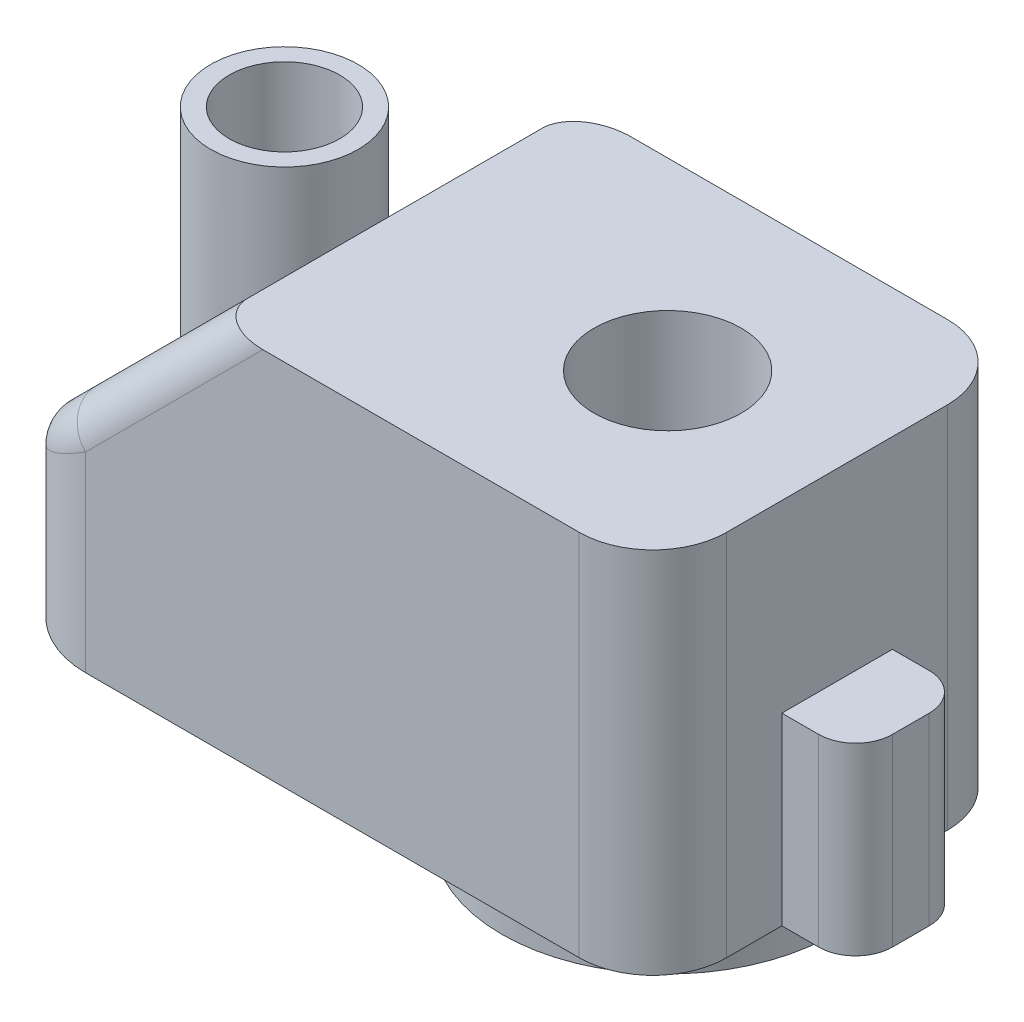
SolidWorks part; units mm, degrees
ref_plane "Alzado" through (0, 0, 0) normal (0, 0, 1) x (1, 0, 0)
ref_plane "Planta" through (0, 0, 0) normal (0, 1, 0) x (1, 0, 0)
ref_plane "Vista lateral" through (0, 0, 0) normal (1, 0, 0) x (0, 0, -1)
sketch "Croquis1" plane through (0, 0, 0) normal (0, 1, 0) x (1, 0, 0)
  line L1 (0, 0) -> (900, 0)
  line L2 (0, 0) -> (0, 500)
  line L3 (0, 500) -> (900, 500)
  line L4 (900, 0) -> (900, 500)
  dimension "D1" = 900
  dimension "D2" = 500
extrude "Saliente-Extruir1" add sketch "Croquis1" along normal blind 500
sketch "Croquis2" plane through (900, 0, 0) normal (1, 0, 0) x (0, 0, -1)
  line L0 (0, 0) -> (500, 0) construction
  line L1 (175, 250) -> (325, 250)
  line L2 (175, 250) -> (175, 0)
  line L3 (175, 0) -> (325, 0)
  line L4 (325, 250) -> (325, 0)
  line L5 (0, 500) -> (0, 0) construction
  point P6 (250, 250)
  dimension "D1" = 150
  dimension "D2" = 250
  dimension "D3" = 250
extrude "Saliente-Extruir2" add sketch "Croquis2" along normal blind 100 separate body
fillet "Redondeo1" radius 50 2 edges at (1000, 125, -325) (1000, 125, -175)
fillet "Redondeo2" radius 100 2 edges at (900, 250, -500) (900, 250, 0)
chamfer "Chaflán1" distance 300 angle 45 1 edges at (0, 500, -250)
fillet "Redondeo5" radius 130 2 edges at (0, 100, -500) (0, 100, 0)
sketch "Croquis3" plane through (0, 500, 0) normal (0, 1, 0) x (1, 0, 0)
  line L2 (130, 500) -> (300, 500) construction
  circle A0 centre (150, 250) radius 100
  dimension "D1" = 150
  dimension "D2" = 250
  dimension "D3" = 200
extrude "Saliente-Extruir3" add sketch "Croquis3" along normal blind 50 and the other way blind 600
sketch "Croquis4" plane through (0, 550, 0) normal (0, 1, 0) x (1, 0, 0)
  line L0 (130, 500) -> (300, 500) construction
  circle A0 centre (150, 250) radius 75
  dimension "D1" = 150
  dimension "D2" = 250
  dimension "D3" = 150
sketch "Croquis5" plane through (0, 0, 0) normal (0, -1, 0) x (1, 0, 0)
  line L0 (130, 0) -> (800, 0) construction
  line L2 (900, -175) -> (900, -325) construction
  circle A0 centre (670, -250) radius 100
  dimension "D1" = 200
  dimension "D2" = 250
  dimension "D3" = 230
extrude "Cortar-Extruir3" cut sketch "Croquis5" against normal through all both and the other way through all
sketch "Croquis7" plane through (0, 0, 0) normal (0, -1, 0) x (1, 0, 0)
  line L1 (25, -375) -> (275, -375)
  line L2 (25, -375) -> (25, -125)
  line L3 (25, -125) -> (275, -125)
  line L4 (275, -375) -> (275, -125)
  circle A0 centre (150, -250) radius 100 construction
  dimension "D1" = 250
  dimension "D2" = 250
  dimension "D3" = 125
  dimension "D4" = 125
extrude "Saliente-Extruir5" add sketch "Croquis7" along normal blind 30
fillet "Redondeo6" radius 50 5 edges at (0, 200, -250) (38.0761, 238.0761, -461.9239) (215, 415, -500) (38.0761, 238.0761, -38.0761) (215, 415, 0)
sketch "Croquis9" plane through (0, 0, 0) normal (0, -1, 0) x (1, 0, 0)
  circle A0 centre (670, -250) radius 225
  circle M9 centre (670, -250) radius 100
  dimension "D1" = 450
extrude "Cortar-Extruir5" cut sketch "Croquis4" against normal through all both and the other way through all
extrude "Saliente-Extruir8" add sketch "Croquis9" along normal blind 50 contours A0 M9 region at (451.364, 0, -250)
